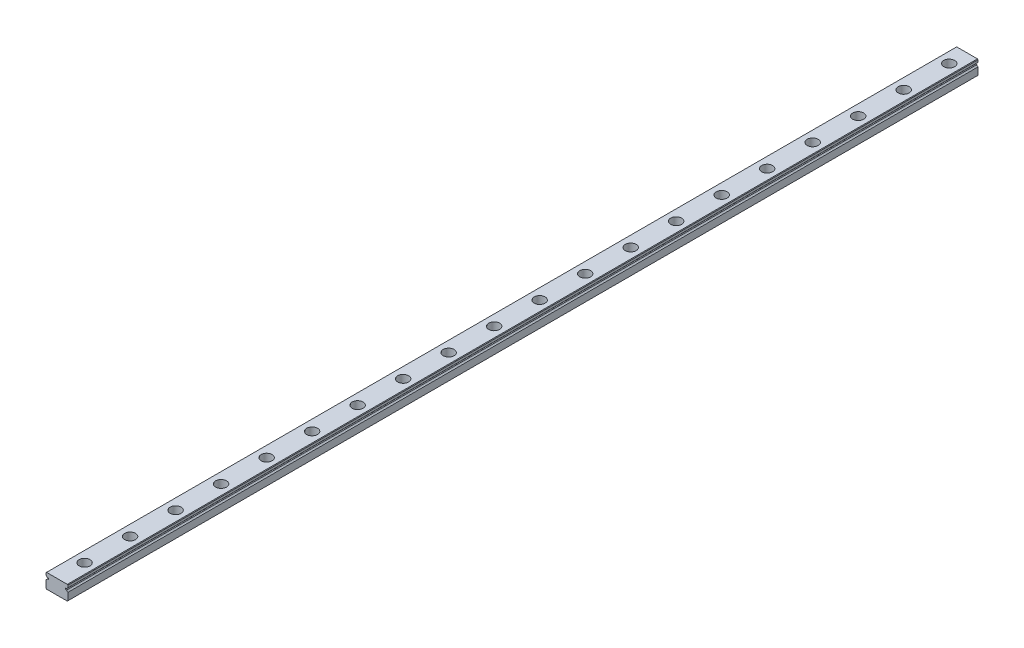
SolidWorks part; units mm, degrees
ref_plane "Спереди" through (0, 0, 0) normal (0, 0, 1) x (1, 0, 0)
ref_plane "Сверху" through (0, 0, 0) normal (0, 1, 0) x (1, 0, 0)
ref_plane "Справа" through (0, 0, 0) normal (1, 0, 0) x (0, 0, -1)
sketch "Эскиз1" plane through (0, 0, 0) normal (0, 0, 1) x (1, 0, 0)
  line L0 (-6, 3.7) -> (-5.7, 4)
  line L1 (-5.7, -4) -> (5.7, -4)
  line L2 (-6, -3.7) -> (-6, 0.3334)
  line L3 (-5.7, 4) -> (5.7, 4)
  line L4 (6, -3.7) -> (6, 0.3334)
  line L5 (-6, -4) -> (6, 4) construction
  line L6 (-6, 4) -> (6, -4) construction
  line L7 (-6, -3.7) -> (-5.7, -4)
  line L8 (5.7, -4) -> (6, -3.7)
  line L9 (5.7, 4) -> (6, 3.7)
  line L10 (-6, 2.4498) -> (-6, 3.7)
  line L11 (-5.2979, 1.7203) -> (-4.6875, 1.7203)
  line L12 (0, 5.4188) -> (0, -5.747) construction
  line L13 (-5.2922, 1.0823) -> (-4.6875, 1.0823)
  line L14 (-4.6875, 1.7203) -> (-4.6875, 1.0823)
  line L15 (4.6875, 1.7203) -> (4.6875, 1.0823)
  line L16 (5.2922, 1.0823) -> (4.6875, 1.0823)
  line L17 (5.2979, 1.7203) -> (4.6875, 1.7203)
  line L18 (6, 2.4498) -> (6, 3.7)
  arc A0 (-6, 0.3334) -> (-5.2922, 1.0823) centre (-6.3695, 1.3916) ccw
  arc A1 (-5.2979, 1.7203) -> (-6, 2.4498) centre (-6.3695, 1.3916) ccw
  arc A2 (5.2979, 1.7203) -> (6, 2.4498) centre (6.3695, 1.3916) cw
  arc A3 (6, 0.3334) -> (5.2922, 1.0823) centre (6.3695, 1.3916) cw
  point P0 (0, 0)
extrude "Бобышка-Вытянуть1" add sketch "Эскиз1" along normal blind 500
sketch "Эскиз2" plane through (0, 4, 0) normal (0, 1, 0) x (1, 0, 0)
  line L0 (0, 0) -> (0, -26.2396) construction
  line L1 (5.7, 0) -> (-5.7, 0) construction
  line L2 (-3.8306, -10) -> (4.207, -10) construction
  circle A0 centre (0.1882, -10) radius 3
  circle A1 centre (0.1882, -10) radius 1.75
  dimension "D1" = 10
extrude "Вырез-Вытянуть1" cut sketch "Эскиз2" against normal blind 4.5
extrude "Вырез-Вытянуть2" cut sketch "Эскиз2<2>" against normal through all contours A1 region at (0.1882, 4, 10)
sketch "Эскиз2<2>" plane through (0, 4, 0) normal (0, 1, 0) x (1, 0, 0) same geometry as "Эскиз2"
pattern_linear "Линейный массив1" count 20 spacing 25 along (0, 0, 1) of "Вырез-Вытянуть1", "Вырез-Вытянуть2"
